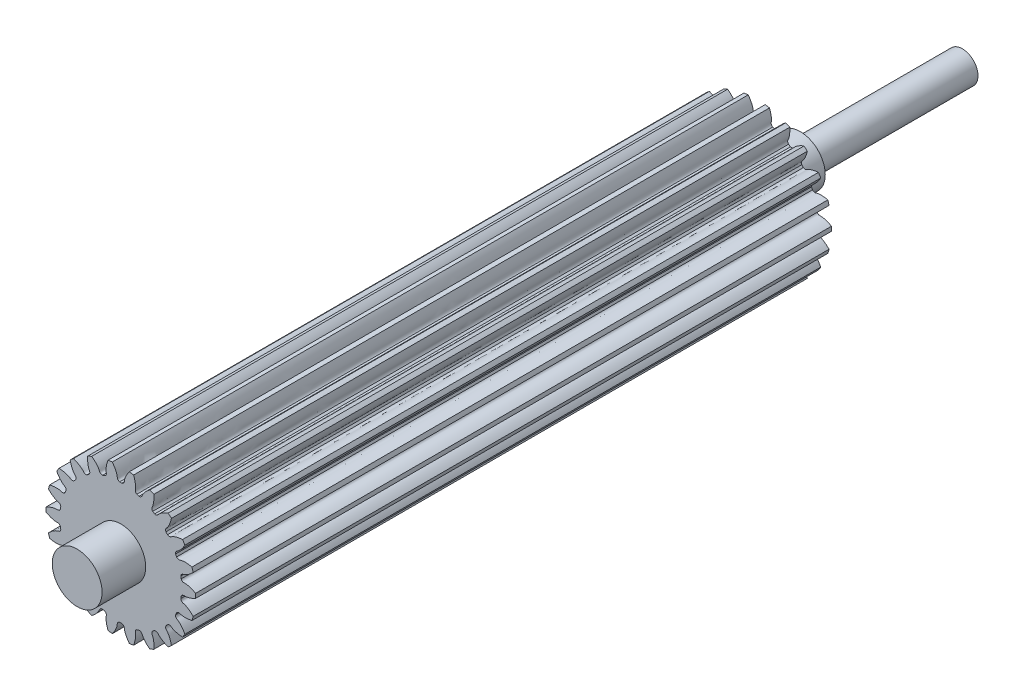
SolidWorks part; units mm, degrees
ref_plane "前视基准面" through (0, 0, 0) normal (0, 0, 1) x (1, 0, 0)
ref_plane "上视基准面" through (0, 0, 0) normal (0, 1, 0) x (1, 0, 0)
ref_plane "右视基准面" through (0, 0, 0) normal (1, 0, 0) x (0, 0, -1)
sketch "草图1" plane through (0, 0, 0) normal (0, 0, 1) x (1, 0, 0)
  circle A0 centre (0, 0) radius 12
extrude "凸台-拉伸1" add sketch "草图1" along normal blind 30
ref_axis "基准轴1" through (0, 0, -1.5) along (0, 0, 1)
sketch "草图2" plane through (0, 0, 0) normal (0, 0, 1) x (1, 0, 0)
  line L0 (0, 0) -> (0, 12) construction
  circle A0 centre (0, 0) radius 12 construction
  arc A1 (0.1857, 9.7482) -> (-0.1857, 9.7482) centre (0, 0) ccw
  arc A2 (3.0856, 13.5599) -> (-3.0856, 13.5599) centre (0, 0) ccw
  spline S0 degree 3 poles (0.1857, 9.7482) (0.5882, 9.8762) (0.5483, 10.1518) (0.5996, 10.4216) (0.606, 10.4519) (0.6139, 10.4862) (0.6235, 10.5243) (0.6349, 10.5661) (0.6484, 10.6117) (0.664, 10.661) (0.6819, 10.7139) (0.7023, 10.7703) (0.7253, 10.8301) (0.7511, 10.8933) (0.7797, 10.9597) (0.8114, 11.0293) (0.8462, 11.1021) (0.8843, 11.1778) (0.9259, 11.2563) (0.9711, 11.3377) (1.0199, 11.4217) (1.0726, 11.5082) (1.1292, 11.5972) (1.1899, 11.6884) (1.2547, 11.7818) (1.3238, 11.8773) (1.3973, 11.9746) (1.4753, 12.0737) (1.5579, 12.1744) (1.6452, 12.2766) (1.7372, 12.3802) (1.8341, 12.4849) (1.9359, 12.5906) (2.0428, 12.6972) (2.1547, 12.8044) (2.2718, 12.9123) (2.3942, 13.0205) (2.5218, 13.1289) (2.6548, 13.2373) (2.8415, 13.3834) (2.9864, 13.49) (3.0856, 13.5599) knots 0 0 0 0 0.157021 0.162531 0.168888 0.176093 0.184146 0.193046 0.202794 0.213389 0.224833 0.237123 0.250262 0.264248 0.279082 0.294763 0.311292 0.328669 0.346893 0.365965 0.385884 0.406652 0.428266 0.450729 0.474039 0.498197 0.523202 0.549055 0.575756 0.603304 0.6317 0.660944 0.691035 0.721974 0.75376 0.786395 0.819876 0.854206 0.889383 0.925408 1 1 1 1
  spline S1 degree 3 poles (-0.1857, 9.7482) (-0.5882, 9.8762) (-0.5483, 10.1518) (-0.5996, 10.4216) (-0.606, 10.4519) (-0.6139, 10.4862) (-0.6235, 10.5243) (-0.6349, 10.5661) (-0.6484, 10.6117) (-0.664, 10.661) (-0.6819, 10.7139) (-0.7023, 10.7703) (-0.7253, 10.8301) (-0.7511, 10.8933) (-0.7797, 10.9597) (-0.8114, 11.0293) (-0.8462, 11.1021) (-0.8843, 11.1778) (-0.9259, 11.2563) (-0.9711, 11.3377) (-1.0199, 11.4217) (-1.0726, 11.5082) (-1.1292, 11.5972) (-1.1899, 11.6884) (-1.2547, 11.7818) (-1.3238, 11.8773) (-1.3973, 11.9746) (-1.4753, 12.0737) (-1.5579, 12.1744) (-1.6452, 12.2766) (-1.7372, 12.3802) (-1.8341, 12.4849) (-1.9359, 12.5906) (-2.0428, 12.6972) (-2.1547, 12.8044) (-2.2718, 12.9123) (-2.3942, 13.0205) (-2.5218, 13.1289) (-2.6548, 13.2373) (-2.8415, 13.3834) (-2.9864, 13.49) (-3.0856, 13.5599) knots 0 0 0 0 0.157021 0.162531 0.168888 0.176093 0.184146 0.193046 0.202794 0.213389 0.224833 0.237123 0.250262 0.264248 0.279082 0.294763 0.311292 0.328669 0.346893 0.365965 0.385884 0.406652 0.428266 0.450729 0.474039 0.498197 0.523202 0.549055 0.575756 0.603304 0.6317 0.660944 0.691035 0.721974 0.75376 0.786395 0.819876 0.854206 0.889383 0.925408 1 1 1 1
extrude "切除-拉伸1" cut sketch "草图2" along normal through all
pattern_circular "阵列(圆周)1" count 22 every 16.364 about axis through (0, 0, -1.5) along (0, 0, 1) of "切除-拉伸1"
sketch "草图3" plane through (0, 0, 0) normal (0, 0, 1) x (1, 0, 0)
  circle A0 centre (0, 0) radius 11 construction
  dimension "Dn" = 22
sketch "草图4" plane through (0, 0, 0) normal (0, 0, -1) x (-1, 0, 0)
  arc A45 (2.9245, 9.3011) -> (2.5682, 9.4057) centre (0, 0) ccw
  arc A46 (2.0557, 11.8226) -> (1.3584, 11.9229) centre (0, 0) ccw
  arc A47 (0.1857, 9.7482) -> (-0.1857, 9.7482) centre (0, 0) ccw
  arc A48 (-1.3584, 11.9229) -> (-2.0557, 11.8226) centre (0, 0) ccw
  arc A49 (-2.5682, 9.4057) -> (-2.9245, 9.3011) centre (0, 0) ccw
  arc A50 (-4.6624, 11.0572) -> (-5.3032, 10.7646) centre (0, 0) ccw
  arc A51 (-5.1141, 8.3011) -> (-5.4265, 8.1004) centre (0, 0) ccw
  arc A52 (-7.5887, 9.2958) -> (-8.1211, 8.8344) centre (0, 0) ccw
  arc A53 (-7.2456, 6.5241) -> (-7.4888, 6.2434) centre (0, 0) ccw
  arc A54 (-9.9003, 6.7812) -> (-10.2811, 6.1886) centre (0, 0) ccw
  arc A55 (-8.7902, 4.2184) -> (-8.9444, 3.8807) centre (0, 0) ccw
  arc A56 (-11.4097, 3.7173) -> (-11.6082, 3.0414) centre (0, 0) ccw
  arc A57 (-9.6226, 1.5711) -> (-9.6754, 1.2035) centre (0, 0) ccw
  arc A58 (-11.9948, 0.3522) -> (-11.9948, -0.3522) centre (0, 0) ccw
  arc A59 (-9.6754, -1.2035) -> (-9.6226, -1.5711) centre (0, 0) ccw
  arc A60 (-11.6082, -3.0414) -> (-11.4097, -3.7173) centre (0, 0) ccw
  arc A61 (-8.9444, -3.8807) -> (-8.7902, -4.2184) centre (0, 0) ccw
  arc A62 (-10.2811, -6.1886) -> (-9.9003, -6.7812) centre (0, 0) ccw
  arc A63 (-7.4888, -6.2434) -> (-7.2456, -6.5241) centre (0, 0) ccw
  arc A64 (-8.1211, -8.8344) -> (-7.5887, -9.2958) centre (0, 0) ccw
  arc A65 (-5.4265, -8.1004) -> (-5.1141, -8.3011) centre (0, 0) ccw
  arc A66 (-5.3032, -10.7646) -> (-4.6624, -11.0572) centre (0, 0) ccw
  arc A67 (-2.9245, -9.3011) -> (-2.5682, -9.4057) centre (0, 0) ccw
  arc A68 (-2.0557, -11.8226) -> (-1.3584, -11.9229) centre (0, 0) ccw
  arc A69 (-0.1857, -9.7482) -> (0.1857, -9.7482) centre (0, 0) ccw
  arc A70 (1.3584, -11.9229) -> (2.0557, -11.8226) centre (0, 0) ccw
  arc A71 (2.5682, -9.4057) -> (2.9245, -9.3011) centre (0, 0) ccw
  arc A72 (4.6624, -11.0572) -> (5.3032, -10.7646) centre (0, 0) ccw
  arc A73 (5.1141, -8.3011) -> (5.4265, -8.1004) centre (0, 0) ccw
  arc A74 (7.5887, -9.2958) -> (8.1211, -8.8344) centre (0, 0) ccw
  arc A75 (7.2456, -6.5241) -> (7.4888, -6.2434) centre (0, 0) ccw
  arc A76 (9.9003, -6.7812) -> (10.2811, -6.1886) centre (0, 0) ccw
  arc A77 (8.7902, -4.2184) -> (8.9444, -3.8807) centre (0, 0) ccw
  arc A78 (11.4097, -3.7173) -> (11.6082, -3.0414) centre (0, 0) ccw
  arc A79 (9.6226, -1.5711) -> (9.6754, -1.2035) centre (0, 0) ccw
  arc A80 (11.9948, -0.3522) -> (11.9948, 0.3522) centre (0, 0) ccw
  arc A81 (9.6754, 1.2035) -> (9.6226, 1.5711) centre (0, 0) ccw
  arc A82 (11.6082, 3.0414) -> (11.4097, 3.7173) centre (0, 0) ccw
  arc A83 (8.9444, 3.8807) -> (8.7902, 4.2184) centre (0, 0) ccw
  arc A84 (10.2811, 6.1886) -> (9.9003, 6.7812) centre (0, 0) ccw
  arc A85 (7.4888, 6.2434) -> (7.2456, 6.5241) centre (0, 0) ccw
  arc A86 (8.1211, 8.8344) -> (7.5887, 9.2958) centre (0, 0) ccw
  arc A87 (5.4265, 8.1004) -> (5.1141, 8.3011) centre (0, 0) ccw
  arc A88 (5.3032, 10.7646) -> (4.6624, 11.0572) centre (0, 0) ccw
  arc A89 (2.9245, 9.3011) -> (2.5682, 9.4057) centre (0, 0) ccw
  arc A90 (2.0557, 11.8226) -> (1.3584, 11.9229) centre (0, 0) ccw
  arc A91 (0.1857, 9.7482) -> (-0.1857, 9.7482) centre (0, 0) ccw
  arc A92 (-1.3584, 11.9229) -> (-2.0557, 11.8226) centre (0, 0) ccw
  arc A93 (-2.5682, 9.4057) -> (-2.9245, 9.3011) centre (0, 0) ccw
  arc A94 (-4.6624, 11.0572) -> (-5.3032, 10.7646) centre (0, 0) ccw
  arc A95 (-5.1141, 8.3011) -> (-5.4265, 8.1004) centre (0, 0) ccw
  arc A96 (-7.5887, 9.2958) -> (-8.1211, 8.8344) centre (0, 0) ccw
  arc A97 (-7.2456, 6.5241) -> (-7.4888, 6.2434) centre (0, 0) ccw
  arc A98 (-9.9003, 6.7812) -> (-10.2811, 6.1886) centre (0, 0) ccw
  arc A99 (-8.7902, 4.2184) -> (-8.9444, 3.8807) centre (0, 0) ccw
  arc A100 (-11.4097, 3.7173) -> (-11.6082, 3.0414) centre (0, 0) ccw
  arc A101 (-9.6226, 1.5711) -> (-9.6754, 1.2035) centre (0, 0) ccw
  arc A102 (-11.9948, 0.3522) -> (-11.9948, -0.3522) centre (0, 0) ccw
  arc A103 (-9.6754, -1.2035) -> (-9.6226, -1.5711) centre (0, 0) ccw
  arc A104 (-11.6082, -3.0414) -> (-11.4097, -3.7173) centre (0, 0) ccw
  arc A105 (-8.9444, -3.8807) -> (-8.7902, -4.2184) centre (0, 0) ccw
  arc A106 (-10.2811, -6.1886) -> (-9.9003, -6.7812) centre (0, 0) ccw
  arc A107 (-7.4888, -6.2434) -> (-7.2456, -6.5241) centre (0, 0) ccw
  arc A108 (-8.1211, -8.8344) -> (-7.5887, -9.2958) centre (0, 0) ccw
  arc A109 (-5.4265, -8.1004) -> (-5.1141, -8.3011) centre (0, 0) ccw
  arc A110 (-5.3032, -10.7646) -> (-4.6624, -11.0572) centre (0, 0) ccw
  arc A111 (-2.9245, -9.3011) -> (-2.5682, -9.4057) centre (0, 0) ccw
  arc A112 (-2.0557, -11.8226) -> (-1.3584, -11.9229) centre (0, 0) ccw
  arc A113 (-0.1857, -9.7482) -> (0.1857, -9.7482) centre (0, 0) ccw
  arc A114 (1.3584, -11.9229) -> (2.0557, -11.8226) centre (0, 0) ccw
  arc A115 (2.5682, -9.4057) -> (2.9245, -9.3011) centre (0, 0) ccw
  arc A116 (4.6624, -11.0572) -> (5.3032, -10.7646) centre (0, 0) ccw
  arc A117 (5.1141, -8.3011) -> (5.4265, -8.1004) centre (0, 0) ccw
  arc A118 (7.5887, -9.2958) -> (8.1211, -8.8344) centre (0, 0) ccw
  arc A119 (7.2456, -6.5241) -> (7.4888, -6.2434) centre (0, 0) ccw
  arc A120 (9.9003, -6.7812) -> (10.2811, -6.1886) centre (0, 0) ccw
  arc A121 (8.7902, -4.2184) -> (8.9444, -3.8807) centre (0, 0) ccw
  arc A122 (11.4097, -3.7173) -> (11.6082, -3.0414) centre (0, 0) ccw
  arc A123 (9.6226, -1.5711) -> (9.6754, -1.2035) centre (0, 0) ccw
  arc A124 (11.9948, -0.3522) -> (11.9948, 0.3522) centre (0, 0) ccw
  arc A125 (9.6754, 1.2035) -> (9.6226, 1.5711) centre (0, 0) ccw
  arc A126 (11.6082, 3.0414) -> (11.4097, 3.7173) centre (0, 0) ccw
  arc A127 (8.9444, 3.8807) -> (8.7902, 4.2184) centre (0, 0) ccw
  arc A128 (10.2811, 6.1886) -> (9.9003, 6.7812) centre (0, 0) ccw
  arc A129 (7.4888, 6.2434) -> (7.2456, 6.5241) centre (0, 0) ccw
  arc A130 (8.1211, 8.8344) -> (7.5887, 9.2958) centre (0, 0) ccw
  arc A131 (5.4265, 8.1004) -> (5.1141, 8.3011) centre (0, 0) ccw
  arc A132 (5.3032, 10.7646) -> (4.6624, 11.0572) centre (0, 0) ccw
  spline S44 degree 3 poles (-9364.1406, 3504.5844) (256.9535, -188.5881) (30.391, 33.0955) (4.2738, 10.7434) (4.1283, 10.6084) (3.9999, 10.4794) (3.888, 10.3576) (3.7917, 10.2441) (3.7102, 10.1398) (3.6518, 10.0587) (3.6037, 9.9872) (3.5713, 9.9359) (3.5381, 9.8795) (3.5167, 9.8409) (0.4171, 3.7881) (50.6224, -28.8281) (-8414.4505, 5403.2739) knots -20.504077 -20.504077 -20.504077 -20.504077 0.549271 0.593348 0.634035 0.671331 0.705237 0.735752 0.762877 0.786611 0.797206 0.815854 0.823907 0.837469 0.842979 5.006087 5.006087 5.006087 5.006087 only from (4.6624, 11.0572) to (2.9245, 9.3011)
  spline S45 degree 3 poles (9998.4358, -3.6711) (-58.166, 3.1168) (1.6971, 3.4126) (2.3619, 10.18) (2.3658, 10.2385) (2.3681, 10.3211) (2.3668, 10.4204) (2.3608, 10.536) (2.3486, 10.6678) (2.329, 10.8154) (2.3007, 10.9784) (2.2624, 11.1562) (2.213, 11.3485) (2.1511, 11.5544) (-9.7414, 46.086) (-333.2574, -33.7791) (9782.7718, -2064.5446) knots -4.005883 -4.005883 -4.005883 -4.005883 0.157021 0.162531 0.176093 0.193046 0.213389 0.237123 0.264248 0.294763 0.328669 0.365965 0.406652 0.450729 0.498197 22.864222 22.864222 22.864222 22.864222 only from (2.5682, 9.4057) to (2.0557, 11.8226)
  spline S46 degree 3 poles (-9972.1826, 724.4408) (299.6765, -108.5568) (19.8359, 40.317) (1.0739, 11.5123) (0.9723, 11.3417) (0.8855, 11.1818) (0.8124, 11.0334) (0.752, 10.8973) (0.7032, 10.7743) (0.6701, 10.6801) (0.644, 10.5979) (0.6274, 10.5396) (0.6113, 10.4761) (0.6018, 10.4331) (-0.667, 3.7521) (56.6936, -13.3983) (-9595.8843, 2813.7787) knots -20.504077 -20.504077 -20.504077 -20.504077 0.549271 0.593348 0.634035 0.671331 0.705237 0.735752 0.762877 0.786611 0.797206 0.815854 0.823907 0.837469 0.842979 5.006087 5.006087 5.006087 5.006087 only from (1.3584, 11.9229) to (0.1857, 9.7482)
  spline S47 degree 3 poles (9594.4631, 2813.3625) (-56.688, -13.3967) (0.6669, 3.7525) (-0.6018, 10.4331) (-0.6145, 10.4903) (-0.6356, 10.5702) (-0.6648, 10.6651) (-0.7032, 10.7743) (-0.752, 10.8973) (-0.8124, 11.0334) (-0.8855, 11.1818) (-0.9723, 11.3417) (-1.0739, 11.5123) (-1.1913, 11.6924) (-22.3307, 41.4748) (-310.2415, -126.3003) (9968.1502, 775.2093) knots -4.005883 -4.005883 -4.005883 -4.005883 0.157021 0.162531 0.176093 0.193046 0.213389 0.237123 0.264248 0.294763 0.328669 0.365965 0.406652 0.450729 0.498197 22.864222 22.864222 22.864222 22.864222 only from (-0.1857, 9.7482) to (-1.3584, 11.9229)
  spline S48 degree 3 poles (-9772.3377, -2114.3927) (318.1215, -19.7309) (7.6738, 44.2723) (-2.213, 11.3485) (-2.2624, 11.1562) (-2.3007, 10.9784) (-2.329, 10.8154) (-2.3486, 10.6678) (-2.3608, 10.536) (-2.366, 10.4362) (-2.3678, 10.3501) (-2.3674, 10.2894) (-2.3649, 10.224) (-2.3619, 10.18) (-1.6971, 3.4122) (58.1719, 3.1168) (-9999.9166, -3.6721) knots -20.504077 -20.504077 -20.504077 -20.504077 0.549271 0.593348 0.634035 0.671331 0.705237 0.735752 0.762877 0.786611 0.797206 0.815854 0.823907 0.837469 0.842979 5.006087 5.006087 5.006087 5.006087 only from (-2.0557, 11.8226) to (-2.5682, 9.4057)
  spline S49 degree 3 poles (8413.2042, 5402.4742) (-50.6175, -28.8249) (-0.4173, 3.7884) (-3.5167, 9.8409) (-3.5451, 9.8922) (-3.5879, 9.963) (-3.6426, 10.0458) (-3.7102, 10.1398) (-3.7917, 10.2441) (-3.888, 10.3576) (-3.9999, 10.4794) (-4.1283, 10.6084) (-4.2738, 10.7434) (-4.4372, 10.8832) (-33.111, 33.5035) (-262.0916, -208.5894) (9345.9684, 3552.1603) knots -4.005883 -4.005883 -4.005883 -4.005883 0.157021 0.162531 0.176093 0.193046 0.213389 0.237123 0.264248 0.294763 0.328669 0.365965 0.406652 0.450729 0.498197 22.864222 22.864222 22.864222 22.864222 only from (-2.9245, 9.3011) to (-4.6624, 11.0572)
  spline S50 degree 3 poles (-8780.7961, -4781.9306) (310.7942, 70.6936) (-5.11, 44.6409) (-5.3206, 10.2653) (-5.3138, 10.0669) (-5.3004, 9.8855) (-5.2817, 9.7211) (-5.2589, 9.574) (-5.2335, 9.4441) (-5.2104, 9.3469) (-5.1879, 9.2637) (-5.1704, 9.2057) (-5.1495, 9.1436) (-5.1343, 9.1022) (-2.5897, 2.7959) (54.9374, 19.3795) (-9593.8152, -2820.8254) knots -20.504077 -20.504077 -20.504077 -20.504077 0.549271 0.593348 0.634035 0.671331 0.705237 0.735752 0.762877 0.786611 0.797206 0.815854 0.823907 0.837469 0.842979 5.006087 5.006087 5.006087 5.006087 only from (-5.3032, 10.7646) to (-5.1141, 8.3011)
  spline S51 degree 3 poles (6550.3574, 7553.9095) (-40.4462, -41.9178) (-1.4677, 3.5173) (-6.1468, 8.4515) (-6.1884, 8.4928) (-6.2494, 8.5486) (-6.3253, 8.6126) (-6.4166, 8.6838) (-6.5242, 8.7609) (-6.6486, 8.8427) (-6.7903, 8.928) (-6.9498, 9.0156) (-7.1274, 9.1041) (-7.3236, 9.1923) (-41.2087, 22.8179) (-192.7087, -273.9798) (7966.6318, 6041.3364) knots -4.005883 -4.005883 -4.005883 -4.005883 0.157021 0.162531 0.176093 0.193046 0.213389 0.237123 0.264248 0.294763 0.328669 0.365965 0.406652 0.450729 0.498197 22.864222 22.864222 22.864222 22.864222 only from (-5.4265, 8.1004) to (-7.5887, 9.2958)
  spline S52 degree 3 poles (-7077.8866, -7062.0649) (278.2882, 155.3908) (-17.4798, 41.393) (-7.9971, 8.3505) (-7.9348, 8.1621) (-7.8708, 7.9917) (-7.8065, 7.8393) (-7.7432, 7.7046) (-7.6822, 7.5871) (-7.6327, 7.5003) (-7.5876, 7.4269) (-7.5545, 7.3761) (-7.517, 7.3224) (-7.4907, 7.287) (-3.2725, 1.953) (47.2522, 34.0721) (-8410.4799, -5409.4523) knots -20.504077 -20.504077 -20.504077 -20.504077 0.549271 0.593348 0.634035 0.671331 0.705237 0.735752 0.762877 0.786611 0.797206 0.815854 0.823907 0.837469 0.842979 5.006087 5.006087 5.006087 5.006087 only from (-8.1211, 8.8344) to (-7.2456, 6.5241)
  spline S53 degree 3 poles (4156.8397, 9093.3721) (-26.9982, -51.6149) (-2.3992, 2.9614) (-8.2789, 6.3774) (-8.3304, 6.4053) (-8.4047, 6.4416) (-8.4955, 6.4817) (-8.6032, 6.5243) (-8.7281, 6.5679) (-8.8705, 6.6114) (-9.0305, 6.6533) (-9.2082, 6.6924) (-9.4036, 6.7273) (-9.6167, 6.7566) (-45.968, 10.2838) (-107.7136, -317.174) (5941.8861, 8041.0794) knots -4.005883 -4.005883 -4.005883 -4.005883 0.157021 0.162531 0.176093 0.193046 0.213389 0.237123 0.264248 0.294763 0.328669 0.365965 0.406652 0.450729 0.498197 22.864222 22.864222 22.864222 22.864222 only from (-7.4888, 6.2434) to (-9.9003, 6.7812)
  spline S54 degree 3 poles (-4801.5689, -8770.0728) (223.2369, 227.4992) (-28.4335, 34.7917) (-10.0258, 5.7592) (-9.9129, 5.596) (-9.8035, 5.4506) (-9.6989, 5.3224) (-9.6002, 5.211) (-9.5086, 5.1155) (-9.4366, 5.0462) (-9.3727, 4.9884) (-9.3266, 4.949) (-9.2755, 4.908) (-9.2403, 4.8814) (-3.6901, 0.952) (35.7389, 46.0045) (-6545.7775, -7559.8374) knots -20.504077 -20.504077 -20.504077 -20.504077 0.549271 0.593348 0.634035 0.671331 0.705237 0.735752 0.762877 0.786611 0.797206 0.815854 0.823907 0.837469 0.842979 5.006087 5.006087 5.006087 5.006087 only from (-10.2811, 6.1886) to (-8.7902, 4.2184)
  spline S55 degree 3 poles (1426.5595, 9896.1437) (-11.363, -57.1304) (-3.1363, 2.1655) (-9.7402, 3.7867) (-9.7976, 3.7989) (-9.8791, 3.8128) (-9.9775, 3.8257) (-10.0928, 3.8362) (-10.225, 3.8429) (-10.3738, 3.8445) (-10.5392, 3.8396) (-10.7207, 3.8271) (-10.918, 3.8055) (-11.1307, 3.7736) (-47.0033, -3.0835) (-13.9922, -334.6726) (3435.7641, 9389.3819) knots -4.005883 -4.005883 -4.005883 -4.005883 0.157021 0.162531 0.176093 0.193046 0.213389 0.237123 0.264248 0.294763 0.328669 0.365965 0.406652 0.450729 0.498197 22.864222 22.864222 22.864222 22.864222 only from (-8.9444, 3.8807) to (-11.4097, 3.7173)
  spline S56 degree 3 poles (-2136.2566, -9767.5815) (150.1003, 281.177) (-37.0837, 25.3717) (-11.2422, 2.7013) (-11.0879, 2.5765) (-10.942, 2.4678) (-10.8055, 2.3743) (-10.6794, 2.2952) (-10.5646, 2.2294) (-10.476, 2.1832) (-10.3984, 2.1457) (-10.3431, 2.1209) (-10.2825, 2.096) (-10.2412, 2.0804) (-3.8089, -0.1262) (21.3303, 54.2098) (-4150.7752, -9097.7696) knots -20.504077 -20.504077 -20.504077 -20.504077 0.549271 0.593348 0.634035 0.671331 0.705237 0.735752 0.762877 0.786611 0.797206 0.815854 0.823907 0.837469 0.842979 5.006087 5.006087 5.006087 5.006087 only from (-11.6082, 3.0414) to (-9.6226, 1.5711)
  spline S57 degree 3 poles (-1419.292, 9897.1886) (5.1928, -58.0175) (-3.6193, 1.1942) (-10.4125, 0.8891) (-10.4709, 0.8847) (-10.5531, 0.8751) (-10.6512, 0.8598) (-10.7647, 0.8373) (-10.8934, 0.8065) (-11.0367, 0.7661) (-11.194, 0.7149) (-11.3647, 0.6517) (-11.5479, 0.5754) (-11.743, 0.4849) (-44.2306, -16.2009) (80.8628, -325.0581) (651.2969, 9977.0126) knots -4.005883 -4.005883 -4.005883 -4.005883 0.157021 0.162531 0.176093 0.193046 0.213389 0.237123 0.264248 0.294763 0.328669 0.365965 0.406652 0.450729 0.498197 22.864222 22.864222 22.864222 22.864222 only from (-9.6754, 1.2035) to (-11.9948, 0.3522)
  spline S58 degree 3 poles (702.1225, -9973.7788) (64.8035, 312.0755) (-42.7296, 13.8963) (-11.5479, -0.5754) (-11.3647, -0.6517) (-11.194, -0.7149) (-11.0367, -0.7661) (-10.8934, -0.8065) (-10.7647, -0.8373) (-10.6667, -0.8567) (-10.5817, -0.8708) (-10.5216, -0.879) (-10.4565, -0.8858) (-10.4125, -0.8891) (-3.619, -1.1942) (5.1936, 58.0233) (-1419.5018, -9898.6545) knots -20.504077 -20.504077 -20.504077 -20.504077 0.549271 0.593348 0.634035 0.671331 0.705237 0.735752 0.762877 0.786611 0.797206 0.815854 0.823907 0.837469 0.842979 5.006087 5.006087 5.006087 5.006087 only from (-11.9948, -0.3522) to (-9.6754, -1.2035)
  spline S59 degree 3 poles (-4150.161, 9096.4221) (21.3278, -54.2044) (-3.8092, 0.1261) (-10.2412, -2.0804) (-10.296, -2.1012) (-10.3722, -2.1335) (-10.4619, -2.1758) (-10.5646, -2.2294) (-10.6794, -2.2952) (-10.8055, -2.3743) (-10.942, -2.4678) (-11.0879, -2.5765) (-11.2422, -2.7014) (-11.4039, -2.8432) (-37.8746, -28.0059) (169.1667, -289.1093) (-2185.9344, 9756.365) knots -4.005883 -4.005883 -4.005883 -4.005883 0.157021 0.162531 0.176093 0.193046 0.213389 0.237123 0.264248 0.294763 0.328669 0.365965 0.406652 0.450729 0.498197 22.864222 22.864222 22.864222 22.864222 only from (-9.6226, -1.5711) to (-11.6082, -3.0414)
  spline S60 degree 3 poles (3483.6198, -9371.9599) (-25.7434, 317.6915) (-44.9138, 1.2951) (-10.918, -3.8055) (-10.7207, -3.8271) (-10.5392, -3.8396) (-10.3738, -3.8445) (-10.225, -3.8429) (-10.0928, -3.8362) (-9.9933, -3.8272) (-9.9078, -3.8167) (-9.8478, -3.8076) (-9.7834, -3.7958) (-9.7402, -3.7867) (-3.136, -2.1654) (-11.3638, 57.1362) (1426.7712, -9897.6093) knots -20.504077 -20.504077 -20.504077 -20.504077 0.549271 0.593348 0.634035 0.671331 0.705237 0.735752 0.762877 0.786611 0.797206 0.815854 0.823907 0.837469 0.842979 5.006087 5.006087 5.006087 5.006087 only from (-11.4097, -3.7173) to (-8.9444, -3.8807)
  spline S61 degree 3 poles (-6544.8086, 7558.7176) (35.7351, -46) (-3.6904, -0.9522) (-9.2403, -4.8814) (-9.287, -4.9168) (-9.351, -4.9692) (-9.4251, -5.0352) (-9.5086, -5.1155) (-9.6002, -5.211) (-9.6989, -5.3224) (-9.8035, -5.4506) (-9.9129, -5.596) (-10.0258, -5.7592) (-10.1409, -5.9408) (-28.4503, -37.542) (243.7658, -229.7385) (-4846.0744, 8745.3148) knots -4.005883 -4.005883 -4.005883 -4.005883 0.157021 0.162531 0.176093 0.193046 0.213389 0.237123 0.264248 0.294763 0.328669 0.365965 0.406652 0.450729 0.498197 22.864222 22.864222 22.864222 22.864222 only from (-8.7902, -4.2184) to (-10.2811, -6.1886)
  spline S62 degree 3 poles (5982.895, -8010.8806) (-114.2046, 297.57) (-43.4593, -11.4111) (-9.4036, -6.7273) (-9.2082, -6.6924) (-9.0305, -6.6533) (-8.8705, -6.6114) (-8.7281, -6.5679) (-8.6032, -6.5243) (-8.5102, -6.4876) (-8.4311, -6.4535) (-8.3761, -6.4279) (-8.3177, -6.3984) (-8.2789, -6.3774) (-2.3989, -2.9612) (-27.0006, 51.6202) (4157.4558, -9094.7187) knots -20.504077 -20.504077 -20.504077 -20.504077 0.549271 0.593348 0.634035 0.671331 0.705237 0.735752 0.762877 0.786611 0.797206 0.815854 0.823907 0.837469 0.842979 5.006087 5.006087 5.006087 5.006087 only from (-9.9003, -6.7812) to (-7.4888, -6.2434)
  spline S63 degree 3 poles (-8409.2347, 5408.6508) (47.2473, -34.069) (-3.2727, -1.9533) (-7.4907, -7.287) (-7.5256, -7.3341) (-7.5722, -7.4024) (-7.6248, -7.4866) (-7.6822, -7.5871) (-7.7432, -7.7046) (-7.8065, -7.8393) (-7.8708, -7.9917) (-7.9348, -8.1621) (-7.9971, -8.3505) (-8.0564, -8.5572) (-16.721, -44.0366) (298.6164, -151.7558) (-7113.6142, 7025.7712) knots -4.005883 -4.005883 -4.005883 -4.005883 0.157021 0.162531 0.176093 0.193046 0.213389 0.237123 0.264248 0.294763 0.328669 0.365965 0.406652 0.450729 0.498197 22.864222 22.864222 22.864222 22.864222 only from (-7.2456, -6.5241) to (-8.1211, -8.8344)
  spline S64 degree 3 poles (7997.4716, -6000.8073) (-193.4137, 253.3412) (-38.484, -23.1927) (-7.1274, -9.1041) (-6.9498, -9.0156) (-6.7903, -8.928) (-6.6486, -8.8427) (-6.5242, -8.7609) (-6.4166, -8.6838) (-6.3378, -8.6224) (-6.2715, -8.5674) (-6.2259, -8.5273) (-6.1781, -8.4826) (-6.1468, -8.4515) (-1.4674, -3.5171) (-40.45, 41.9223) (6551.3279, -7555.028) knots -20.504077 -20.504077 -20.504077 -20.504077 0.549271 0.593348 0.634035 0.671331 0.705237 0.735752 0.762877 0.786611 0.797206 0.815854 0.823907 0.837469 0.842979 5.006087 5.006087 5.006087 5.006087 only from (-7.5887, -9.2958) to (-5.4265, -8.1004)
  spline S65 degree 3 poles (-9592.3946, 2820.4073) (54.9318, -19.3779) (-2.5898, -2.7962) (-5.1343, -9.1022) (-5.1545, -9.1572) (-5.18, -9.2359) (-5.2067, -9.3315) (-5.2335, -9.4441) (-5.2589, -9.574) (-5.2817, -9.7211) (-5.3004, -9.8855) (-5.3138, -10.0669) (-5.3206, -10.2653) (-5.3192, -10.4804) (-3.6372, -46.9637) (329.2748, -61.4786) (-8804.8513, 4737.0413) knots -4.005883 -4.005883 -4.005883 -4.005883 0.157021 0.162531 0.176093 0.193046 0.213389 0.237123 0.264248 0.294763 0.328669 0.365965 0.406652 0.450729 0.498197 22.864222 22.864222 22.864222 22.864222 only from (-5.1141, -8.3011) to (-5.3032, -10.7646)
  spline S66 degree 3 poles (9364.1406, -3504.5844) (-256.9535, 188.5881) (-30.391, -33.0955) (-4.2738, -10.7434) (-4.1283, -10.6084) (-3.9999, -10.4794) (-3.888, -10.3576) (-3.7917, -10.2441) (-3.7102, -10.1398) (-3.6518, -10.0587) (-3.6037, -9.9872) (-3.5713, -9.9359) (-3.5381, -9.8795) (-3.5167, -9.8409) (-0.4171, -3.7881) (-50.6224, 28.8281) (8414.4505, -5403.2739) knots -20.504077 -20.504077 -20.504077 -20.504077 0.549271 0.593348 0.634035 0.671331 0.705237 0.735752 0.762877 0.786611 0.797206 0.815854 0.823907 0.837469 0.842979 5.006087 5.006087 5.006087 5.006087 only from (-4.6624, -11.0572) to (-2.9245, -9.3011)
  spline S67 degree 3 poles (-9998.4358, 3.6711) (58.166, -3.1168) (-1.6971, -3.4126) (-2.3619, -10.18) (-2.3658, -10.2385) (-2.3681, -10.3211) (-2.3668, -10.4204) (-2.3608, -10.536) (-2.3486, -10.6678) (-2.329, -10.8154) (-2.3007, -10.9784) (-2.2624, -11.1562) (-2.213, -11.3485) (-2.1511, -11.5544) (9.7414, -46.086) (333.2574, 33.7791) (-9782.7718, 2064.5446) knots -4.005883 -4.005883 -4.005883 -4.005883 0.157021 0.162531 0.176093 0.193046 0.213389 0.237123 0.264248 0.294763 0.328669 0.365965 0.406652 0.450729 0.498197 22.864222 22.864222 22.864222 22.864222 only from (-2.5682, -9.4057) to (-2.0557, -11.8226)
  spline S68 degree 3 poles (9972.1826, -724.4408) (-299.6765, 108.5568) (-19.8359, -40.317) (-1.0739, -11.5123) (-0.9723, -11.3417) (-0.8855, -11.1818) (-0.8124, -11.0334) (-0.752, -10.8973) (-0.7032, -10.7743) (-0.6701, -10.6801) (-0.644, -10.5979) (-0.6274, -10.5396) (-0.6113, -10.4761) (-0.6018, -10.4331) (0.667, -3.7521) (-56.6936, 13.3983) (9595.8843, -2813.7787) knots -20.504077 -20.504077 -20.504077 -20.504077 0.549271 0.593348 0.634035 0.671331 0.705237 0.735752 0.762877 0.786611 0.797206 0.815854 0.823907 0.837469 0.842979 5.006087 5.006087 5.006087 5.006087 only from (-1.3584, -11.9229) to (-0.1857, -9.7482)
  spline S69 degree 3 poles (-9594.4631, -2813.3625) (56.688, 13.3967) (-0.6669, -3.7525) (0.6018, -10.4331) (0.6145, -10.4903) (0.6356, -10.5702) (0.6648, -10.6651) (0.7032, -10.7743) (0.752, -10.8973) (0.8124, -11.0334) (0.8855, -11.1818) (0.9723, -11.3417) (1.0739, -11.5123) (1.1913, -11.6924) (22.3307, -41.4748) (310.2415, 126.3003) (-9968.1502, -775.2093) knots -4.005883 -4.005883 -4.005883 -4.005883 0.157021 0.162531 0.176093 0.193046 0.213389 0.237123 0.264248 0.294763 0.328669 0.365965 0.406652 0.450729 0.498197 22.864222 22.864222 22.864222 22.864222 only from (0.1857, -9.7482) to (1.3584, -11.9229)
  spline S70 degree 3 poles (9772.3377, 2114.3927) (-318.1215, 19.7309) (-7.6738, -44.2723) (2.213, -11.3485) (2.2624, -11.1562) (2.3007, -10.9784) (2.329, -10.8154) (2.3486, -10.6678) (2.3608, -10.536) (2.366, -10.4362) (2.3678, -10.3501) (2.3674, -10.2894) (2.3649, -10.224) (2.3619, -10.18) (1.6971, -3.4122) (-58.1719, -3.1168) (9999.9166, 3.6721) knots -20.504077 -20.504077 -20.504077 -20.504077 0.549271 0.593348 0.634035 0.671331 0.705237 0.735752 0.762877 0.786611 0.797206 0.815854 0.823907 0.837469 0.842979 5.006087 5.006087 5.006087 5.006087 only from (2.0557, -11.8226) to (2.5682, -9.4057)
  spline S71 degree 3 poles (-8413.2042, -5402.4742) (50.6175, 28.8249) (0.4173, -3.7884) (3.5167, -9.8409) (3.5451, -9.8922) (3.5879, -9.963) (3.6426, -10.0458) (3.7102, -10.1398) (3.7917, -10.2441) (3.888, -10.3576) (3.9999, -10.4794) (4.1283, -10.6084) (4.2738, -10.7434) (4.4372, -10.8832) (33.111, -33.5035) (262.0916, 208.5894) (-9345.9684, -3552.1603) knots -4.005883 -4.005883 -4.005883 -4.005883 0.157021 0.162531 0.176093 0.193046 0.213389 0.237123 0.264248 0.294763 0.328669 0.365965 0.406652 0.450729 0.498197 22.864222 22.864222 22.864222 22.864222 only from (2.9245, -9.3011) to (4.6624, -11.0572)
  spline S72 degree 3 poles (8780.7961, 4781.9306) (-310.7942, -70.6936) (5.11, -44.6409) (5.3206, -10.2653) (5.3138, -10.0669) (5.3004, -9.8855) (5.2817, -9.7211) (5.2589, -9.574) (5.2335, -9.4441) (5.2104, -9.3469) (5.1879, -9.2637) (5.1704, -9.2057) (5.1495, -9.1436) (5.1343, -9.1022) (2.5897, -2.7959) (-54.9374, -19.3795) (9593.8152, 2820.8254) knots -20.504077 -20.504077 -20.504077 -20.504077 0.549271 0.593348 0.634035 0.671331 0.705237 0.735752 0.762877 0.786611 0.797206 0.815854 0.823907 0.837469 0.842979 5.006087 5.006087 5.006087 5.006087 only from (5.3032, -10.7646) to (5.1141, -8.3011)
  spline S73 degree 3 poles (-6550.3574, -7553.9095) (40.4462, 41.9178) (1.4677, -3.5173) (6.1468, -8.4515) (6.1884, -8.4928) (6.2494, -8.5486) (6.3253, -8.6126) (6.4166, -8.6838) (6.5242, -8.7609) (6.6486, -8.8427) (6.7903, -8.928) (6.9498, -9.0156) (7.1274, -9.1041) (7.3236, -9.1923) (41.2087, -22.8179) (192.7087, 273.9798) (-7966.6318, -6041.3364) knots -4.005883 -4.005883 -4.005883 -4.005883 0.157021 0.162531 0.176093 0.193046 0.213389 0.237123 0.264248 0.294763 0.328669 0.365965 0.406652 0.450729 0.498197 22.864222 22.864222 22.864222 22.864222 only from (5.4265, -8.1004) to (7.5887, -9.2958)
  spline S74 degree 3 poles (7077.8866, 7062.0649) (-278.2882, -155.3908) (17.4798, -41.393) (7.9971, -8.3505) (7.9348, -8.1621) (7.8708, -7.9917) (7.8065, -7.8393) (7.7432, -7.7046) (7.6822, -7.5871) (7.6327, -7.5003) (7.5876, -7.4269) (7.5545, -7.3761) (7.517, -7.3224) (7.4907, -7.287) (3.2725, -1.953) (-47.2522, -34.0721) (8410.4799, 5409.4523) knots -20.504077 -20.504077 -20.504077 -20.504077 0.549271 0.593348 0.634035 0.671331 0.705237 0.735752 0.762877 0.786611 0.797206 0.815854 0.823907 0.837469 0.842979 5.006087 5.006087 5.006087 5.006087 only from (8.1211, -8.8344) to (7.2456, -6.5241)
  spline S75 degree 3 poles (-4156.8397, -9093.3721) (26.9982, 51.6149) (2.3992, -2.9614) (8.2789, -6.3774) (8.3304, -6.4053) (8.4047, -6.4416) (8.4955, -6.4817) (8.6032, -6.5243) (8.7281, -6.5679) (8.8705, -6.6114) (9.0305, -6.6533) (9.2082, -6.6924) (9.4036, -6.7273) (9.6167, -6.7566) (45.968, -10.2838) (107.7136, 317.174) (-5941.8861, -8041.0794) knots -4.005883 -4.005883 -4.005883 -4.005883 0.157021 0.162531 0.176093 0.193046 0.213389 0.237123 0.264248 0.294763 0.328669 0.365965 0.406652 0.450729 0.498197 22.864222 22.864222 22.864222 22.864222 only from (7.4888, -6.2434) to (9.9003, -6.7812)
  spline S76 degree 3 poles (4801.5689, 8770.0728) (-223.2369, -227.4992) (28.4335, -34.7917) (10.0258, -5.7592) (9.9129, -5.596) (9.8035, -5.4506) (9.6989, -5.3224) (9.6002, -5.211) (9.5086, -5.1155) (9.4366, -5.0462) (9.3727, -4.9884) (9.3266, -4.949) (9.2755, -4.908) (9.2403, -4.8814) (3.6901, -0.952) (-35.7389, -46.0045) (6545.7775, 7559.8374) knots -20.504077 -20.504077 -20.504077 -20.504077 0.549271 0.593348 0.634035 0.671331 0.705237 0.735752 0.762877 0.786611 0.797206 0.815854 0.823907 0.837469 0.842979 5.006087 5.006087 5.006087 5.006087 only from (10.2811, -6.1886) to (8.7902, -4.2184)
  spline S77 degree 3 poles (-1426.5595, -9896.1437) (11.363, 57.1304) (3.1363, -2.1655) (9.7402, -3.7867) (9.7976, -3.7989) (9.8791, -3.8128) (9.9775, -3.8257) (10.0928, -3.8362) (10.225, -3.8429) (10.3738, -3.8445) (10.5392, -3.8396) (10.7207, -3.8271) (10.918, -3.8055) (11.1307, -3.7736) (47.0033, 3.0835) (13.9922, 334.6726) (-3435.7641, -9389.3819) knots -4.005883 -4.005883 -4.005883 -4.005883 0.157021 0.162531 0.176093 0.193046 0.213389 0.237123 0.264248 0.294763 0.328669 0.365965 0.406652 0.450729 0.498197 22.864222 22.864222 22.864222 22.864222 only from (8.9444, -3.8807) to (11.4097, -3.7173)
  spline S78 degree 3 poles (2136.2566, 9767.5815) (-150.1003, -281.177) (37.0837, -25.3717) (11.2422, -2.7013) (11.0879, -2.5765) (10.942, -2.4678) (10.8055, -2.3743) (10.6794, -2.2952) (10.5646, -2.2294) (10.476, -2.1832) (10.3984, -2.1457) (10.3431, -2.1209) (10.2825, -2.096) (10.2412, -2.0804) (3.8089, 0.1262) (-21.3303, -54.2098) (4150.7752, 9097.7696) knots -20.504077 -20.504077 -20.504077 -20.504077 0.549271 0.593348 0.634035 0.671331 0.705237 0.735752 0.762877 0.786611 0.797206 0.815854 0.823907 0.837469 0.842979 5.006087 5.006087 5.006087 5.006087 only from (11.6082, -3.0414) to (9.6226, -1.5711)
  spline S79 degree 3 poles (1419.292, -9897.1886) (-5.1928, 58.0175) (3.6193, -1.1942) (10.4125, -0.8891) (10.4709, -0.8847) (10.5531, -0.8751) (10.6512, -0.8598) (10.7647, -0.8373) (10.8934, -0.8065) (11.0367, -0.7661) (11.194, -0.7149) (11.3647, -0.6517) (11.5479, -0.5754) (11.743, -0.4849) (44.2306, 16.2009) (-80.8628, 325.0581) (-651.2969, -9977.0126) knots -4.005883 -4.005883 -4.005883 -4.005883 0.157021 0.162531 0.176093 0.193046 0.213389 0.237123 0.264248 0.294763 0.328669 0.365965 0.406652 0.450729 0.498197 22.864222 22.864222 22.864222 22.864222 only from (9.6754, -1.2035) to (11.9948, -0.3522)
  spline S80 degree 3 poles (-702.1225, 9973.7788) (-64.8035, -312.0755) (42.7296, -13.8963) (11.5479, 0.5754) (11.3647, 0.6517) (11.194, 0.7149) (11.0367, 0.7661) (10.8934, 0.8065) (10.7647, 0.8373) (10.6667, 0.8567) (10.5817, 0.8708) (10.5216, 0.879) (10.4565, 0.8858) (10.4125, 0.8891) (3.619, 1.1942) (-5.1936, -58.0233) (1419.5018, 9898.6545) knots -20.504077 -20.504077 -20.504077 -20.504077 0.549271 0.593348 0.634035 0.671331 0.705237 0.735752 0.762877 0.786611 0.797206 0.815854 0.823907 0.837469 0.842979 5.006087 5.006087 5.006087 5.006087 only from (11.9948, 0.3522) to (9.6754, 1.2035)
  spline S81 degree 3 poles (4150.161, -9096.4221) (-21.3278, 54.2044) (3.8092, -0.1261) (10.2412, 2.0804) (10.296, 2.1012) (10.3722, 2.1335) (10.4619, 2.1758) (10.5646, 2.2294) (10.6794, 2.2952) (10.8055, 2.3743) (10.942, 2.4678) (11.0879, 2.5765) (11.2422, 2.7014) (11.4039, 2.8432) (37.8746, 28.0059) (-169.1667, 289.1093) (2185.9344, -9756.365) knots -4.005883 -4.005883 -4.005883 -4.005883 0.157021 0.162531 0.176093 0.193046 0.213389 0.237123 0.264248 0.294763 0.328669 0.365965 0.406652 0.450729 0.498197 22.864222 22.864222 22.864222 22.864222 only from (9.6226, 1.5711) to (11.6082, 3.0414)
  spline S82 degree 3 poles (-3483.6198, 9371.9599) (25.7434, -317.6915) (44.9138, -1.2951) (10.918, 3.8055) (10.7207, 3.8271) (10.5392, 3.8396) (10.3738, 3.8445) (10.225, 3.8429) (10.0928, 3.8362) (9.9933, 3.8272) (9.9078, 3.8167) (9.8478, 3.8076) (9.7834, 3.7958) (9.7402, 3.7867) (3.136, 2.1654) (11.3638, -57.1362) (-1426.7712, 9897.6093) knots -20.504077 -20.504077 -20.504077 -20.504077 0.549271 0.593348 0.634035 0.671331 0.705237 0.735752 0.762877 0.786611 0.797206 0.815854 0.823907 0.837469 0.842979 5.006087 5.006087 5.006087 5.006087 only from (11.4097, 3.7173) to (8.9444, 3.8807)
  spline S83 degree 3 poles (6544.8086, -7558.7176) (-35.7351, 46) (3.6904, 0.9522) (9.2403, 4.8814) (9.287, 4.9168) (9.351, 4.9692) (9.4251, 5.0352) (9.5086, 5.1155) (9.6002, 5.211) (9.6989, 5.3224) (9.8035, 5.4506) (9.9129, 5.596) (10.0258, 5.7592) (10.1409, 5.9408) (28.4503, 37.542) (-243.7658, 229.7385) (4846.0744, -8745.3148) knots -4.005883 -4.005883 -4.005883 -4.005883 0.157021 0.162531 0.176093 0.193046 0.213389 0.237123 0.264248 0.294763 0.328669 0.365965 0.406652 0.450729 0.498197 22.864222 22.864222 22.864222 22.864222 only from (8.7902, 4.2184) to (10.2811, 6.1886)
  spline S84 degree 3 poles (-5982.895, 8010.8806) (114.2046, -297.57) (43.4593, 11.4111) (9.4036, 6.7273) (9.2082, 6.6924) (9.0305, 6.6533) (8.8705, 6.6114) (8.7281, 6.5679) (8.6032, 6.5243) (8.5102, 6.4876) (8.4311, 6.4535) (8.3761, 6.4279) (8.3177, 6.3984) (8.2789, 6.3774) (2.3989, 2.9612) (27.0006, -51.6202) (-4157.4558, 9094.7187) knots -20.504077 -20.504077 -20.504077 -20.504077 0.549271 0.593348 0.634035 0.671331 0.705237 0.735752 0.762877 0.786611 0.797206 0.815854 0.823907 0.837469 0.842979 5.006087 5.006087 5.006087 5.006087 only from (9.9003, 6.7812) to (7.4888, 6.2434)
  spline S85 degree 3 poles (8409.2347, -5408.6508) (-47.2473, 34.069) (3.2727, 1.9533) (7.4907, 7.287) (7.5256, 7.3341) (7.5722, 7.4024) (7.6248, 7.4866) (7.6822, 7.5871) (7.7432, 7.7046) (7.8065, 7.8393) (7.8708, 7.9917) (7.9348, 8.1621) (7.9971, 8.3505) (8.0564, 8.5572) (16.721, 44.0366) (-298.6164, 151.7558) (7113.6142, -7025.7712) knots -4.005883 -4.005883 -4.005883 -4.005883 0.157021 0.162531 0.176093 0.193046 0.213389 0.237123 0.264248 0.294763 0.328669 0.365965 0.406652 0.450729 0.498197 22.864222 22.864222 22.864222 22.864222 only from (7.2456, 6.5241) to (8.1211, 8.8344)
  spline S86 degree 3 poles (-7997.4716, 6000.8073) (193.4137, -253.3412) (38.484, 23.1927) (7.1274, 9.1041) (6.9498, 9.0156) (6.7903, 8.928) (6.6486, 8.8427) (6.5242, 8.7609) (6.4166, 8.6838) (6.3378, 8.6224) (6.2715, 8.5674) (6.2259, 8.5273) (6.1781, 8.4826) (6.1468, 8.4515) (1.4674, 3.5171) (40.45, -41.9223) (-6551.3279, 7555.028) knots -20.504077 -20.504077 -20.504077 -20.504077 0.549271 0.593348 0.634035 0.671331 0.705237 0.735752 0.762877 0.786611 0.797206 0.815854 0.823907 0.837469 0.842979 5.006087 5.006087 5.006087 5.006087 only from (7.5887, 9.2958) to (5.4265, 8.1004)
  spline S87 degree 3 poles (9592.3946, -2820.4073) (-54.9318, 19.3779) (2.5898, 2.7962) (5.1343, 9.1022) (5.1545, 9.1572) (5.18, 9.2359) (5.2067, 9.3315) (5.2335, 9.4441) (5.2589, 9.574) (5.2817, 9.7211) (5.3004, 9.8855) (5.3138, 10.0669) (5.3206, 10.2653) (5.3192, 10.4804) (3.6372, 46.9637) (-329.2748, 61.4786) (8804.8513, -4737.0413) knots -4.005883 -4.005883 -4.005883 -4.005883 0.157021 0.162531 0.176093 0.193046 0.213389 0.237123 0.264248 0.294763 0.328669 0.365965 0.406652 0.450729 0.498197 22.864222 22.864222 22.864222 22.864222 only from (5.1141, 8.3011) to (5.3032, 10.7646)
  spline S88 degree 3 poles (4.6624, 11.0572) (4.5848, 10.9995) (4.452, 10.8959) (4.2738, 10.7434) (4.1283, 10.6084) (3.9999, 10.4794) (3.888, 10.3576) (3.7917, 10.2441) (3.7102, 10.1398) (3.6518, 10.0587) (3.6037, 9.9872) (3.5713, 9.9359) (3.5381, 9.8795) (3.5167, 9.8409) (3.3862, 9.5861) (3.3468, 9.3104) (2.9245, 9.3011) knots 0.48979 0.48979 0.48979 0.48979 0.549271 0.593348 0.634035 0.671331 0.705237 0.735752 0.762877 0.786611 0.797206 0.815854 0.823907 0.837469 0.842979 1 1 1 1
  spline S89 degree 3 poles (2.5682, 9.4057) (2.2181, 9.6418) (2.334, 9.895) (2.3619, 10.18) (2.3658, 10.2385) (2.3681, 10.3211) (2.3668, 10.4204) (2.3608, 10.536) (2.3486, 10.6678) (2.329, 10.8154) (2.3007, 10.9784) (2.2624, 11.1562) (2.213, 11.3485) (2.1511, 11.5544) (2.0963, 11.7137) (2.0626, 11.8043) (2.0557, 11.8226) knots 0 0 0 0 0.157021 0.162531 0.176093 0.193046 0.213389 0.237123 0.264248 0.294763 0.328669 0.365965 0.406652 0.450729 0.498197 0.51021 0.51021 0.51021 0.51021
  spline S90 degree 3 poles (1.3584, 11.9229) (1.3002, 11.8457) (1.2019, 11.7088) (1.0739, 11.5123) (0.9723, 11.3417) (0.8855, 11.1818) (0.8124, 11.0334) (0.752, 10.8973) (0.7032, 10.7743) (0.6701, 10.6801) (0.644, 10.5979) (0.6274, 10.5396) (0.6113, 10.4761) (0.6018, 10.4331) (0.5483, 10.1518) (0.5882, 9.8762) (0.1857, 9.7482) knots 0.48979 0.48979 0.48979 0.48979 0.549271 0.593348 0.634035 0.671331 0.705237 0.735752 0.762877 0.786611 0.797206 0.815854 0.823907 0.837469 0.842979 1 1 1 1
  spline S91 degree 3 poles (-0.1857, 9.7482) (-0.5882, 9.8762) (-0.5483, 10.1518) (-0.6018, 10.4331) (-0.6145, 10.4903) (-0.6356, 10.5702) (-0.6648, 10.6651) (-0.7032, 10.7743) (-0.752, 10.8973) (-0.8124, 11.0334) (-0.8855, 11.1818) (-0.9723, 11.3417) (-1.0739, 11.5123) (-1.1913, 11.6924) (-1.2888, 11.8298) (-1.3466, 11.9073) (-1.3584, 11.9229) knots 0 0 0 0 0.157021 0.162531 0.176093 0.193046 0.213389 0.237123 0.264248 0.294763 0.328669 0.365965 0.406652 0.450729 0.498197 0.51021 0.51021 0.51021 0.51021
  spline S92 degree 3 poles (-2.0557, 11.8226) (-2.0898, 11.7321) (-2.1455, 11.5732) (-2.213, 11.3485) (-2.2624, 11.1562) (-2.3007, 10.9784) (-2.329, 10.8154) (-2.3486, 10.6678) (-2.3608, 10.536) (-2.366, 10.4362) (-2.3678, 10.3501) (-2.3674, 10.2894) (-2.3649, 10.224) (-2.3619, 10.18) (-2.334, 9.895) (-2.2181, 9.6418) (-2.5682, 9.4057) knots 0.48979 0.48979 0.48979 0.48979 0.549271 0.593348 0.634035 0.671331 0.705237 0.735752 0.762877 0.786611 0.797206 0.815854 0.823907 0.837469 0.842979 1 1 1 1
  spline S93 degree 3 poles (-2.9245, 9.3011) (-3.3468, 9.3104) (-3.3862, 9.5861) (-3.5167, 9.8409) (-3.5451, 9.8922) (-3.5879, 9.963) (-3.6426, 10.0458) (-3.7102, 10.1398) (-3.7917, 10.2441) (-3.888, 10.3576) (-3.9999, 10.4794) (-4.1283, 10.6084) (-4.2738, 10.7434) (-4.4372, 10.8832) (-4.5694, 10.9875) (-4.6468, 11.0456) (-4.6624, 11.0572) knots 0 0 0 0 0.157021 0.162531 0.176093 0.193046 0.213389 0.237123 0.264248 0.294763 0.328669 0.365965 0.406652 0.450729 0.498197 0.51021 0.51021 0.51021 0.51021
  spline S94 degree 3 poles (-5.3032, 10.7646) (-5.3105, 10.6681) (-5.3191, 10.4999) (-5.3206, 10.2653) (-5.3138, 10.0669) (-5.3004, 9.8855) (-5.2817, 9.7211) (-5.2589, 9.574) (-5.2335, 9.4441) (-5.2104, 9.3469) (-5.1879, 9.2637) (-5.1704, 9.2057) (-5.1495, 9.1436) (-5.1343, 9.1022) (-5.0272, 8.8367) (-4.8447, 8.6264) (-5.1141, 8.3011) knots 0.48979 0.48979 0.48979 0.48979 0.549271 0.593348 0.634035 0.671331 0.705237 0.735752 0.762877 0.786611 0.797206 0.815854 0.823907 0.837469 0.842979 1 1 1 1
  spline S95 degree 3 poles (-5.4265, 8.1004) (-5.8343, 7.9904) (-5.9498, 8.2438) (-6.1468, 8.4515) (-6.1884, 8.4928) (-6.2494, 8.5486) (-6.3253, 8.6126) (-6.4166, 8.6838) (-6.5242, 8.7609) (-6.6486, 8.8427) (-6.7903, 8.928) (-6.9498, 9.0156) (-7.1274, 9.1041) (-7.3236, 9.1923) (-7.4798, 9.2551) (-7.5704, 9.289) (-7.5887, 9.2958) knots 0 0 0 0 0.157021 0.162531 0.176093 0.193046 0.213389 0.237123 0.264248 0.294763 0.328669 0.365965 0.406652 0.450729 0.498197 0.51021 0.51021 0.51021 0.51021
  spline S96 degree 3 poles (-8.1211, 8.8344) (-8.1009, 8.7398) (-8.0618, 8.576) (-7.9971, 8.3505) (-7.9348, 8.1621) (-7.8708, 7.9917) (-7.8065, 7.8393) (-7.7432, 7.7046) (-7.6822, 7.5871) (-7.6327, 7.5003) (-7.5876, 7.4269) (-7.5545, 7.3761) (-7.517, 7.3224) (-7.4907, 7.287) (-7.3131, 7.0624) (-7.0788, 6.912) (-7.2456, 6.5241) knots 0.48979 0.48979 0.48979 0.48979 0.549271 0.593348 0.634035 0.671331 0.705237 0.735752 0.762877 0.786611 0.797206 0.815854 0.823907 0.837469 0.842979 1 1 1 1
  spline S97 degree 3 poles (-7.4888, 6.2434) (-7.8491, 6.023) (-8.0313, 6.2336) (-8.2789, 6.3774) (-8.3304, 6.4053) (-8.4047, 6.4416) (-8.4955, 6.4817) (-8.6032, 6.5243) (-8.7281, 6.5679) (-8.8705, 6.6114) (-9.0305, 6.6533) (-9.2082, 6.6924) (-9.4036, 6.7273) (-9.6167, 6.7566) (-9.7843, 6.7729) (-9.8808, 6.7799) (-9.9003, 6.7812) knots 0 0 0 0 0.157021 0.162531 0.176093 0.193046 0.213389 0.237123 0.264248 0.294763 0.328669 0.365965 0.406652 0.450729 0.498197 0.51021 0.51021 0.51021 0.51021
  spline S98 degree 3 poles (-10.2811, 6.1886) (-10.2351, 6.1035) (-10.1514, 5.9573) (-10.0258, 5.7592) (-9.9129, 5.596) (-9.8035, 5.4506) (-9.6989, 5.3224) (-9.6002, 5.211) (-9.5086, 5.1155) (-9.4366, 5.0462) (-9.3727, 4.9884) (-9.3266, 4.949) (-9.2755, 4.908) (-9.2403, 4.8814) (-9.0066, 4.716) (-8.7394, 4.6377) (-8.7902, 4.2184) knots 0.48979 0.48979 0.48979 0.48979 0.549271 0.593348 0.634035 0.671331 0.705237 0.735752 0.762877 0.786611 0.797206 0.815854 0.823907 0.837469 0.842979 1 1 1 1
  spline S99 degree 3 poles (-8.9444, 3.8807) (-9.228, 3.5677) (-9.4622, 3.7184) (-9.7402, 3.7867) (-9.7976, 3.7989) (-9.8791, 3.8128) (-9.9775, 3.8257) (-10.0928, 3.8362) (-10.225, 3.8429) (-10.3738, 3.8445) (-10.5392, 3.8396) (-10.7207, 3.8271) (-10.918, 3.8055) (-11.1307, 3.7736) (-11.2961, 3.742) (-11.3906, 3.7215) (-11.4097, 3.7173) knots 0 0 0 0 0.157021 0.162531 0.176093 0.193046 0.213389 0.237123 0.264248 0.294763 0.328669 0.365965 0.406652 0.450729 0.498197 0.51021 0.51021 0.51021 0.51021
  spline S100 degree 3 poles (-11.6082, 3.0414) (-11.5401, 2.9727) (-11.4186, 2.8561) (-11.2422, 2.7013) (-11.0879, 2.5765) (-10.942, 2.4678) (-10.8055, 2.3743) (-10.6794, 2.2952) (-10.5646, 2.2294) (-10.476, 2.1832) (-10.3984, 2.1457) (-10.3431, 2.1209) (-10.2825, 2.096) (-10.2412, 2.0804) (-9.9704, 1.9875) (-9.692, 1.9877) (-9.6226, 1.5711) knots 0.48979 0.48979 0.48979 0.48979 0.549271 0.593348 0.634035 0.671331 0.705237 0.735752 0.762877 0.786611 0.797206 0.815854 0.823907 0.837469 0.842979 1 1 1 1
  spline S101 degree 3 poles (-9.6754, 1.2035) (-9.8594, 0.8234) (-10.1265, 0.902) (-10.4125, 0.8891) (-10.4709, 0.8847) (-10.5531, 0.8751) (-10.6512, 0.8598) (-10.7647, 0.8373) (-10.8934, 0.8065) (-11.0367, 0.7661) (-11.194, 0.7149) (-11.3647, 0.6517) (-11.5479, 0.5754) (-11.743, 0.4849) (-11.8928, 0.4079) (-11.9777, 0.3617) (-11.9948, 0.3522) knots 0 0 0 0 0.157021 0.162531 0.176093 0.193046 0.213389 0.237123 0.264248 0.294763 0.328669 0.365965 0.406652 0.450729 0.498197 0.51021 0.51021 0.51021 0.51021
  spline S102 degree 3 poles (-11.9948, -0.3522) (-11.9101, -0.3989) (-11.7607, -0.4766) (-11.5479, -0.5754) (-11.3647, -0.6517) (-11.194, -0.7149) (-11.0367, -0.7661) (-10.8934, -0.8065) (-10.7647, -0.8373) (-10.6667, -0.8567) (-10.5817, -0.8708) (-10.5216, -0.879) (-10.4565, -0.8858) (-10.4125, -0.8891) (-10.1265, -0.902) (-9.8594, -0.8234) (-9.6754, -1.2035) knots 0.48979 0.48979 0.48979 0.48979 0.549271 0.593348 0.634035 0.671331 0.705237 0.735752 0.762877 0.786611 0.797206 0.815854 0.823907 0.837469 0.842979 1 1 1 1
  spline S103 degree 3 poles (-9.6226, -1.5711) (-9.692, -1.9877) (-9.9704, -1.9875) (-10.2412, -2.0804) (-10.296, -2.1012) (-10.3722, -2.1335) (-10.4619, -2.1758) (-10.5646, -2.2294) (-10.6794, -2.2952) (-10.8055, -2.3743) (-10.942, -2.4678) (-11.0879, -2.5765) (-11.2422, -2.7014) (-11.4039, -2.8432) (-11.526, -2.9592) (-11.5944, -3.0275) (-11.6082, -3.0414) knots 0 0 0 0 0.157021 0.162531 0.176093 0.193046 0.213389 0.237123 0.264248 0.294763 0.328669 0.365965 0.406652 0.450729 0.498197 0.51021 0.51021 0.51021 0.51021
  spline S104 degree 3 poles (-11.4097, -3.7173) (-11.3153, -3.7382) (-11.15, -3.7707) (-10.918, -3.8055) (-10.7207, -3.8271) (-10.5392, -3.8396) (-10.3738, -3.8445) (-10.225, -3.8429) (-10.0928, -3.8362) (-9.9933, -3.8272) (-9.9078, -3.8167) (-9.8478, -3.8076) (-9.7834, -3.7958) (-9.7402, -3.7867) (-9.4622, -3.7184) (-9.228, -3.5677) (-8.9444, -3.8807) knots 0.48979 0.48979 0.48979 0.48979 0.549271 0.593348 0.634035 0.671331 0.705237 0.735752 0.762877 0.786611 0.797206 0.815854 0.823907 0.837469 0.842979 1 1 1 1
  spline S105 degree 3 poles (-8.7902, -4.2184) (-8.7394, -4.6377) (-9.0066, -4.716) (-9.2403, -4.8814) (-9.287, -4.9168) (-9.351, -4.9692) (-9.4251, -5.0352) (-9.5086, -5.1155) (-9.6002, -5.211) (-9.6989, -5.3224) (-9.8035, -5.4506) (-9.9129, -5.596) (-10.0258, -5.7592) (-10.1409, -5.9408) (-10.2254, -6.0866) (-10.2718, -6.1714) (-10.2811, -6.1886) knots 0 0 0 0 0.157021 0.162531 0.176093 0.193046 0.213389 0.237123 0.264248 0.294763 0.328669 0.365965 0.406652 0.450729 0.498197 0.51021 0.51021 0.51021 0.51021
  spline S106 degree 3 poles (-9.9003, -6.7812) (-9.8038, -6.7747) (-9.636, -6.7593) (-9.4036, -6.7273) (-9.2082, -6.6924) (-9.0305, -6.6533) (-8.8705, -6.6114) (-8.7281, -6.5679) (-8.6032, -6.5243) (-8.5102, -6.4876) (-8.4311, -6.4535) (-8.3761, -6.4279) (-8.3177, -6.3984) (-8.2789, -6.3774) (-8.0313, -6.2336) (-7.8491, -6.023) (-7.4888, -6.2434) knots 0.48979 0.48979 0.48979 0.48979 0.549271 0.593348 0.634035 0.671331 0.705237 0.735752 0.762877 0.786611 0.797206 0.815854 0.823907 0.837469 0.842979 1 1 1 1
  spline S107 degree 3 poles (-7.2456, -6.5241) (-7.0788, -6.912) (-7.3131, -7.0624) (-7.4907, -7.287) (-7.5256, -7.3341) (-7.5722, -7.4024) (-7.6248, -7.4866) (-7.6822, -7.5871) (-7.7432, -7.7046) (-7.8065, -7.8393) (-7.8708, -7.9917) (-7.9348, -8.1621) (-7.9971, -8.3505) (-8.0564, -8.5572) (-8.0964, -8.7208) (-8.1171, -8.8153) (-8.1211, -8.8344) knots 0 0 0 0 0.157021 0.162531 0.176093 0.193046 0.213389 0.237123 0.264248 0.294763 0.328669 0.365965 0.406652 0.450729 0.498197 0.51021 0.51021 0.51021 0.51021
  spline S108 degree 3 poles (-7.5887, -9.2958) (-7.498, -9.2623) (-7.3414, -9.2003) (-7.1274, -9.1041) (-6.9498, -9.0156) (-6.7903, -8.928) (-6.6486, -8.8427) (-6.5242, -8.7609) (-6.4166, -8.6838) (-6.3378, -8.6224) (-6.2715, -8.5674) (-6.2259, -8.5273) (-6.1781, -8.4826) (-6.1468, -8.4515) (-5.9498, -8.2438) (-5.8343, -7.9904) (-5.4265, -8.1004) knots 0.48979 0.48979 0.48979 0.48979 0.549271 0.593348 0.634035 0.671331 0.705237 0.735752 0.762877 0.786611 0.797206 0.815854 0.823907 0.837469 0.842979 1 1 1 1
  spline S109 degree 3 poles (-5.1141, -8.3011) (-4.8447, -8.6264) (-5.0272, -8.8367) (-5.1343, -9.1022) (-5.1545, -9.1572) (-5.18, -9.2359) (-5.2067, -9.3315) (-5.2335, -9.4441) (-5.2589, -9.574) (-5.2817, -9.7211) (-5.3004, -9.8855) (-5.3138, -10.0669) (-5.3206, -10.2653) (-5.3192, -10.4804) (-5.3115, -10.6486) (-5.3047, -10.7451) (-5.3032, -10.7646) knots 0 0 0 0 0.157021 0.162531 0.176093 0.193046 0.213389 0.237123 0.264248 0.294763 0.328669 0.365965 0.406652 0.450729 0.498197 0.51021 0.51021 0.51021 0.51021
  spline S110 degree 3 poles (-4.6624, -11.0572) (-4.5848, -10.9995) (-4.452, -10.8959) (-4.2738, -10.7434) (-4.1283, -10.6084) (-3.9999, -10.4794) (-3.888, -10.3576) (-3.7917, -10.2441) (-3.7102, -10.1398) (-3.6518, -10.0587) (-3.6037, -9.9872) (-3.5713, -9.9359) (-3.5381, -9.8795) (-3.5167, -9.8409) (-3.3862, -9.5861) (-3.3468, -9.3104) (-2.9245, -9.3011) knots 0.48979 0.48979 0.48979 0.48979 0.549271 0.593348 0.634035 0.671331 0.705237 0.735752 0.762877 0.786611 0.797206 0.815854 0.823907 0.837469 0.842979 1 1 1 1
  spline S111 degree 3 poles (-2.5682, -9.4057) (-2.2181, -9.6418) (-2.334, -9.895) (-2.3619, -10.18) (-2.3658, -10.2385) (-2.3681, -10.3211) (-2.3668, -10.4204) (-2.3608, -10.536) (-2.3486, -10.6678) (-2.329, -10.8154) (-2.3007, -10.9784) (-2.2624, -11.1562) (-2.213, -11.3485) (-2.1511, -11.5544) (-2.0963, -11.7137) (-2.0626, -11.8043) (-2.0557, -11.8226) knots 0 0 0 0 0.157021 0.162531 0.176093 0.193046 0.213389 0.237123 0.264248 0.294763 0.328669 0.365965 0.406652 0.450729 0.498197 0.51021 0.51021 0.51021 0.51021
  spline S112 degree 3 poles (-1.3584, -11.9229) (-1.3002, -11.8457) (-1.2019, -11.7088) (-1.0739, -11.5123) (-0.9723, -11.3417) (-0.8855, -11.1818) (-0.8124, -11.0334) (-0.752, -10.8973) (-0.7032, -10.7743) (-0.6701, -10.6801) (-0.644, -10.5979) (-0.6274, -10.5396) (-0.6113, -10.4761) (-0.6018, -10.4331) (-0.5483, -10.1518) (-0.5882, -9.8762) (-0.1857, -9.7482) knots 0.48979 0.48979 0.48979 0.48979 0.549271 0.593348 0.634035 0.671331 0.705237 0.735752 0.762877 0.786611 0.797206 0.815854 0.823907 0.837469 0.842979 1 1 1 1
  spline S113 degree 3 poles (0.1857, -9.7482) (0.5882, -9.8762) (0.5483, -10.1518) (0.6018, -10.4331) (0.6145, -10.4903) (0.6356, -10.5702) (0.6648, -10.6651) (0.7032, -10.7743) (0.752, -10.8973) (0.8124, -11.0334) (0.8855, -11.1818) (0.9723, -11.3417) (1.0739, -11.5123) (1.1913, -11.6924) (1.2888, -11.8298) (1.3466, -11.9073) (1.3584, -11.9229) knots 0 0 0 0 0.157021 0.162531 0.176093 0.193046 0.213389 0.237123 0.264248 0.294763 0.328669 0.365965 0.406652 0.450729 0.498197 0.51021 0.51021 0.51021 0.51021
  spline S114 degree 3 poles (2.0557, -11.8226) (2.0898, -11.7321) (2.1455, -11.5732) (2.213, -11.3485) (2.2624, -11.1562) (2.3007, -10.9784) (2.329, -10.8154) (2.3486, -10.6678) (2.3608, -10.536) (2.366, -10.4362) (2.3678, -10.3501) (2.3674, -10.2894) (2.3649, -10.224) (2.3619, -10.18) (2.334, -9.895) (2.2181, -9.6418) (2.5682, -9.4057) knots 0.48979 0.48979 0.48979 0.48979 0.549271 0.593348 0.634035 0.671331 0.705237 0.735752 0.762877 0.786611 0.797206 0.815854 0.823907 0.837469 0.842979 1 1 1 1
  spline S115 degree 3 poles (2.9245, -9.3011) (3.3468, -9.3104) (3.3862, -9.5861) (3.5167, -9.8409) (3.5451, -9.8922) (3.5879, -9.963) (3.6426, -10.0458) (3.7102, -10.1398) (3.7917, -10.2441) (3.888, -10.3576) (3.9999, -10.4794) (4.1283, -10.6084) (4.2738, -10.7434) (4.4372, -10.8832) (4.5694, -10.9875) (4.6468, -11.0456) (4.6624, -11.0572) knots 0 0 0 0 0.157021 0.162531 0.176093 0.193046 0.213389 0.237123 0.264248 0.294763 0.328669 0.365965 0.406652 0.450729 0.498197 0.51021 0.51021 0.51021 0.51021
  spline S116 degree 3 poles (5.3032, -10.7646) (5.3105, -10.6681) (5.3191, -10.4999) (5.3206, -10.2653) (5.3138, -10.0669) (5.3004, -9.8855) (5.2817, -9.7211) (5.2589, -9.574) (5.2335, -9.4441) (5.2104, -9.3469) (5.1879, -9.2637) (5.1704, -9.2057) (5.1495, -9.1436) (5.1343, -9.1022) (5.0272, -8.8367) (4.8447, -8.6264) (5.1141, -8.3011) knots 0.48979 0.48979 0.48979 0.48979 0.549271 0.593348 0.634035 0.671331 0.705237 0.735752 0.762877 0.786611 0.797206 0.815854 0.823907 0.837469 0.842979 1 1 1 1
  spline S117 degree 3 poles (5.4265, -8.1004) (5.8343, -7.9904) (5.9498, -8.2438) (6.1468, -8.4515) (6.1884, -8.4928) (6.2494, -8.5486) (6.3253, -8.6126) (6.4166, -8.6838) (6.5242, -8.7609) (6.6486, -8.8427) (6.7903, -8.928) (6.9498, -9.0156) (7.1274, -9.1041) (7.3236, -9.1923) (7.4798, -9.2551) (7.5704, -9.289) (7.5887, -9.2958) knots 0 0 0 0 0.157021 0.162531 0.176093 0.193046 0.213389 0.237123 0.264248 0.294763 0.328669 0.365965 0.406652 0.450729 0.498197 0.51021 0.51021 0.51021 0.51021
  spline S118 degree 3 poles (8.1211, -8.8344) (8.1009, -8.7398) (8.0618, -8.576) (7.9971, -8.3505) (7.9348, -8.1621) (7.8708, -7.9917) (7.8065, -7.8393) (7.7432, -7.7046) (7.6822, -7.5871) (7.6327, -7.5003) (7.5876, -7.4269) (7.5545, -7.3761) (7.517, -7.3224) (7.4907, -7.287) (7.3131, -7.0624) (7.0788, -6.912) (7.2456, -6.5241) knots 0.48979 0.48979 0.48979 0.48979 0.549271 0.593348 0.634035 0.671331 0.705237 0.735752 0.762877 0.786611 0.797206 0.815854 0.823907 0.837469 0.842979 1 1 1 1
  spline S119 degree 3 poles (7.4888, -6.2434) (7.8491, -6.023) (8.0313, -6.2336) (8.2789, -6.3774) (8.3304, -6.4053) (8.4047, -6.4416) (8.4955, -6.4817) (8.6032, -6.5243) (8.7281, -6.5679) (8.8705, -6.6114) (9.0305, -6.6533) (9.2082, -6.6924) (9.4036, -6.7273) (9.6167, -6.7566) (9.7843, -6.7729) (9.8808, -6.7799) (9.9003, -6.7812) knots 0 0 0 0 0.157021 0.162531 0.176093 0.193046 0.213389 0.237123 0.264248 0.294763 0.328669 0.365965 0.406652 0.450729 0.498197 0.51021 0.51021 0.51021 0.51021
  spline S120 degree 3 poles (10.2811, -6.1886) (10.2351, -6.1035) (10.1514, -5.9573) (10.0258, -5.7592) (9.9129, -5.596) (9.8035, -5.4506) (9.6989, -5.3224) (9.6002, -5.211) (9.5086, -5.1155) (9.4366, -5.0462) (9.3727, -4.9884) (9.3266, -4.949) (9.2755, -4.908) (9.2403, -4.8814) (9.0066, -4.716) (8.7394, -4.6377) (8.7902, -4.2184) knots 0.48979 0.48979 0.48979 0.48979 0.549271 0.593348 0.634035 0.671331 0.705237 0.735752 0.762877 0.786611 0.797206 0.815854 0.823907 0.837469 0.842979 1 1 1 1
  spline S121 degree 3 poles (8.9444, -3.8807) (9.228, -3.5677) (9.4622, -3.7184) (9.7402, -3.7867) (9.7976, -3.7989) (9.8791, -3.8128) (9.9775, -3.8257) (10.0928, -3.8362) (10.225, -3.8429) (10.3738, -3.8445) (10.5392, -3.8396) (10.7207, -3.8271) (10.918, -3.8055) (11.1307, -3.7736) (11.2961, -3.742) (11.3906, -3.7215) (11.4097, -3.7173) knots 0 0 0 0 0.157021 0.162531 0.176093 0.193046 0.213389 0.237123 0.264248 0.294763 0.328669 0.365965 0.406652 0.450729 0.498197 0.51021 0.51021 0.51021 0.51021
  spline S122 degree 3 poles (11.6082, -3.0414) (11.5401, -2.9727) (11.4186, -2.8561) (11.2422, -2.7013) (11.0879, -2.5765) (10.942, -2.4678) (10.8055, -2.3743) (10.6794, -2.2952) (10.5646, -2.2294) (10.476, -2.1832) (10.3984, -2.1457) (10.3431, -2.1209) (10.2825, -2.096) (10.2412, -2.0804) (9.9704, -1.9875) (9.692, -1.9877) (9.6226, -1.5711) knots 0.48979 0.48979 0.48979 0.48979 0.549271 0.593348 0.634035 0.671331 0.705237 0.735752 0.762877 0.786611 0.797206 0.815854 0.823907 0.837469 0.842979 1 1 1 1
  spline S123 degree 3 poles (9.6754, -1.2035) (9.8594, -0.8234) (10.1265, -0.902) (10.4125, -0.8891) (10.4709, -0.8847) (10.5531, -0.8751) (10.6512, -0.8598) (10.7647, -0.8373) (10.8934, -0.8065) (11.0367, -0.7661) (11.194, -0.7149) (11.3647, -0.6517) (11.5479, -0.5754) (11.743, -0.4849) (11.8928, -0.4079) (11.9777, -0.3617) (11.9948, -0.3522) knots 0 0 0 0 0.157021 0.162531 0.176093 0.193046 0.213389 0.237123 0.264248 0.294763 0.328669 0.365965 0.406652 0.450729 0.498197 0.51021 0.51021 0.51021 0.51021
  spline S124 degree 3 poles (11.9948, 0.3522) (11.9101, 0.3989) (11.7607, 0.4766) (11.5479, 0.5754) (11.3647, 0.6517) (11.194, 0.7149) (11.0367, 0.7661) (10.8934, 0.8065) (10.7647, 0.8373) (10.6667, 0.8567) (10.5817, 0.8708) (10.5216, 0.879) (10.4565, 0.8858) (10.4125, 0.8891) (10.1265, 0.902) (9.8594, 0.8234) (9.6754, 1.2035) knots 0.48979 0.48979 0.48979 0.48979 0.549271 0.593348 0.634035 0.671331 0.705237 0.735752 0.762877 0.786611 0.797206 0.815854 0.823907 0.837469 0.842979 1 1 1 1
  spline S125 degree 3 poles (9.6226, 1.5711) (9.692, 1.9877) (9.9704, 1.9875) (10.2412, 2.0804) (10.296, 2.1012) (10.3722, 2.1335) (10.4619, 2.1758) (10.5646, 2.2294) (10.6794, 2.2952) (10.8055, 2.3743) (10.942, 2.4678) (11.0879, 2.5765) (11.2422, 2.7014) (11.4039, 2.8432) (11.526, 2.9592) (11.5944, 3.0275) (11.6082, 3.0414) knots 0 0 0 0 0.157021 0.162531 0.176093 0.193046 0.213389 0.237123 0.264248 0.294763 0.328669 0.365965 0.406652 0.450729 0.498197 0.51021 0.51021 0.51021 0.51021
  spline S126 degree 3 poles (11.4097, 3.7173) (11.3153, 3.7382) (11.15, 3.7707) (10.918, 3.8055) (10.7207, 3.8271) (10.5392, 3.8396) (10.3738, 3.8445) (10.225, 3.8429) (10.0928, 3.8362) (9.9933, 3.8272) (9.9078, 3.8167) (9.8478, 3.8076) (9.7834, 3.7958) (9.7402, 3.7867) (9.4622, 3.7184) (9.228, 3.5677) (8.9444, 3.8807) knots 0.48979 0.48979 0.48979 0.48979 0.549271 0.593348 0.634035 0.671331 0.705237 0.735752 0.762877 0.786611 0.797206 0.815854 0.823907 0.837469 0.842979 1 1 1 1
  spline S127 degree 3 poles (8.7902, 4.2184) (8.7394, 4.6377) (9.0066, 4.716) (9.2403, 4.8814) (9.287, 4.9168) (9.351, 4.9692) (9.4251, 5.0352) (9.5086, 5.1155) (9.6002, 5.211) (9.6989, 5.3224) (9.8035, 5.4506) (9.9129, 5.596) (10.0258, 5.7592) (10.1409, 5.9408) (10.2254, 6.0866) (10.2718, 6.1714) (10.2811, 6.1886) knots 0 0 0 0 0.157021 0.162531 0.176093 0.193046 0.213389 0.237123 0.264248 0.294763 0.328669 0.365965 0.406652 0.450729 0.498197 0.51021 0.51021 0.51021 0.51021
  spline S128 degree 3 poles (9.9003, 6.7812) (9.8038, 6.7747) (9.636, 6.7593) (9.4036, 6.7273) (9.2082, 6.6924) (9.0305, 6.6533) (8.8705, 6.6114) (8.7281, 6.5679) (8.6032, 6.5243) (8.5102, 6.4876) (8.4311, 6.4535) (8.3761, 6.4279) (8.3177, 6.3984) (8.2789, 6.3774) (8.0313, 6.2336) (7.8491, 6.023) (7.4888, 6.2434) knots 0.48979 0.48979 0.48979 0.48979 0.549271 0.593348 0.634035 0.671331 0.705237 0.735752 0.762877 0.786611 0.797206 0.815854 0.823907 0.837469 0.842979 1 1 1 1
  spline S129 degree 3 poles (7.2456, 6.5241) (7.0788, 6.912) (7.3131, 7.0624) (7.4907, 7.287) (7.5256, 7.3341) (7.5722, 7.4024) (7.6248, 7.4866) (7.6822, 7.5871) (7.7432, 7.7046) (7.8065, 7.8393) (7.8708, 7.9917) (7.9348, 8.1621) (7.9971, 8.3505) (8.0564, 8.5572) (8.0964, 8.7208) (8.1171, 8.8153) (8.1211, 8.8344) knots 0 0 0 0 0.157021 0.162531 0.176093 0.193046 0.213389 0.237123 0.264248 0.294763 0.328669 0.365965 0.406652 0.450729 0.498197 0.51021 0.51021 0.51021 0.51021
  spline S130 degree 3 poles (7.5887, 9.2958) (7.498, 9.2623) (7.3414, 9.2003) (7.1274, 9.1041) (6.9498, 9.0156) (6.7903, 8.928) (6.6486, 8.8427) (6.5242, 8.7609) (6.4166, 8.6838) (6.3378, 8.6224) (6.2715, 8.5674) (6.2259, 8.5273) (6.1781, 8.4826) (6.1468, 8.4515) (5.9498, 8.2438) (5.8343, 7.9904) (5.4265, 8.1004) knots 0.48979 0.48979 0.48979 0.48979 0.549271 0.593348 0.634035 0.671331 0.705237 0.735752 0.762877 0.786611 0.797206 0.815854 0.823907 0.837469 0.842979 1 1 1 1
  spline S131 degree 3 poles (5.1141, 8.3011) (4.8447, 8.6264) (5.0272, 8.8367) (5.1343, 9.1022) (5.1545, 9.1572) (5.18, 9.2359) (5.2067, 9.3315) (5.2335, 9.4441) (5.2589, 9.574) (5.2817, 9.7211) (5.3004, 9.8855) (5.3138, 10.0669) (5.3206, 10.2653) (5.3192, 10.4804) (5.3115, 10.6486) (5.3047, 10.7451) (5.3032, 10.7646) knots 0 0 0 0 0.157021 0.162531 0.176093 0.193046 0.213389 0.237123 0.264248 0.294763 0.328669 0.365965 0.406652 0.450729 0.498197 0.51021 0.51021 0.51021 0.51021
  dimension "D1" = 0
extrude "凸台-拉伸2" add sketch "草图4" along normal blind 72
sketch "草图5" plane through (0, 0, -72) normal (0, 0, -1) x (-1, 0, 0)
  circle A0 centre (0, 0) radius 9.5
  circle A1 centre (0, 0) radius 6.95
  dimension "D1" = 13.9
  dimension "D2" = 19
sketch "草图6" plane through (0, 0, 30) normal (0, 0, 1) x (1, 0, 0)
  circle A0 centre (0, 0) radius 7.0436
sketch "草图8" plane through (0, 0, 30) normal (0, 0, 1) x (1, 0, 0)
  circle A0 centre (0, 0) radius 12
sketch "草图9" plane through (0, 0, 30) normal (0, 0, 1) x (1, 0, 0)
  circle A0 centre (0, 0) radius 4.9335
  dimension "D1" = 9.8671
sketch "草图10" plane through (0, 0, -72) normal (0, 0, -1) x (-1, 0, 0)
  circle A0 centre (0, 0) radius 12
sketch "草图11" plane through (0, 0, -72) normal (0, 0, -1) x (-1, 0, 0)
  circle A0 centre (0, 0) radius 9
  dimension "D1" = 18
sketch "草图12" plane through (0, 0, -72) normal (0, 0, -1) x (-1, 0, 0)
  circle A0 centre (0, 0) radius 5
  dimension "D1" = 10
sketch "草图16" plane through (0, 0, 30) normal (0, 0, 1) x (1, 0, 0)
  circle A0 centre (0, 0) radius 6.95
  dimension "D1" = 13.9
sketch "草图18" plane through (0, 0, -72) normal (0, 0, -1) x (-1, 0, 0)
  circle A0 centre (0, 0) radius 4
  dimension "D1" = 8
sketch "草图19" plane through (0, 0, -72) normal (0, 0, -1) x (-1, 0, 0)
  circle A0 centre (0, 0) radius 4
  dimension "D1" = 8
extrude "凸台-拉伸3" add sketch "草图19" along normal blind 7
sketch "草图20" plane through (0, 0, 30) normal (0, 0, 1) x (1, 0, 0)
  circle A0 centre (0, 0) radius 4
  dimension "D1" = 8
extrude "凸台-拉伸4" add sketch "草图20" along normal blind 7
sketch "草图21" plane through (0, 0, -79) normal (0, 0, -1) x (-1, 0, 0)
  circle A0 centre (0, 0) radius 2.5
  dimension "D1" = 5
extrude "凸台-拉伸5" add sketch "草图21" along normal blind 26
